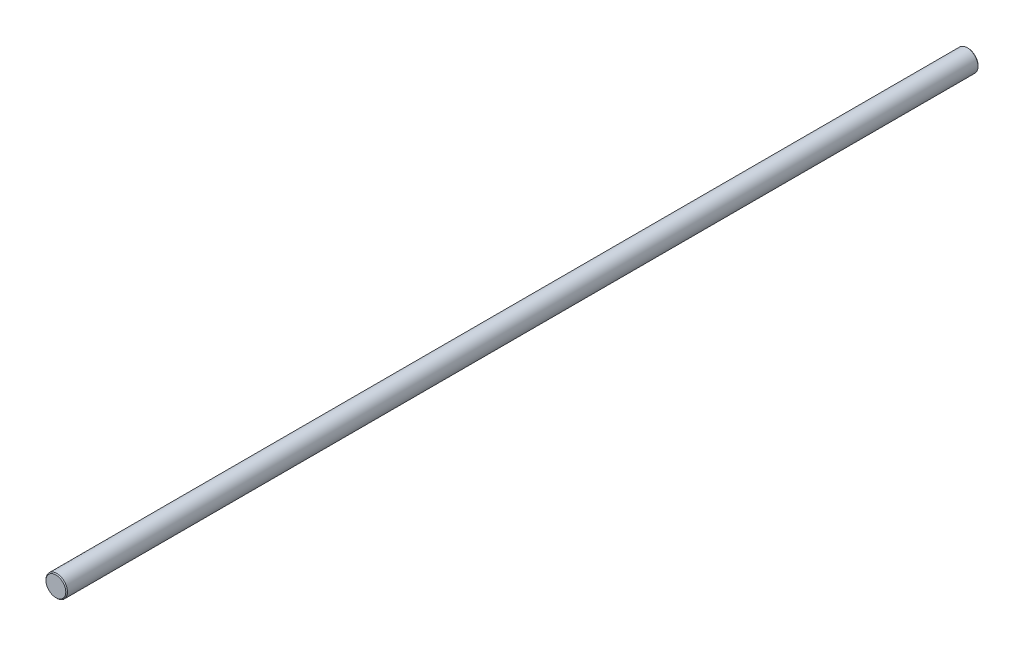
SolidWorks part; units mm, degrees
material "AISI 304"
ref_plane "Спереди" through (0, 0, 0) normal (0, 0, 1) x (1, 0, 0)
ref_plane "Сверху" through (0, 0, 0) normal (0, 1, 0) x (1, 0, 0)
ref_plane "Справа" through (0, 0, 0) normal (1, 0, 0) x (0, 0, -1)
ref_axis "ОсьX" through (-88.99, 0, 0) along (1, 0, 0)
ref_axis "ОсьZ" through (0, 55, 0) along (0, -1, 0)
ref_axis "ОсьY" through (0, 0, -88.99) along (0, 0, 1)
sketch "Эскиз1" plane through (0, 0, 0) normal (0, 0, 1) x (1, 0, 0)
  circle A0 centre (0, 0) radius 12.5
  dimension "D1" = 25
extrude "Бобышка-Вытянуть1" add sketch "Эскиз1" along normal mid plane 1060
chamfer "Фаска1" distance 1 angle 45 2 edges at (12.5, 0, -530) (12.5, 0, 530)
